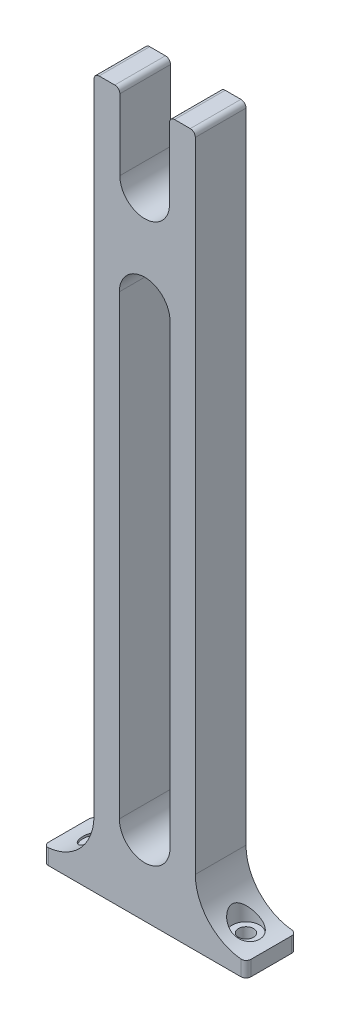
SolidWorks part; units mm, degrees
ref_plane "Front Plane" through (0, 0, 0) normal (0, 0, 1) x (1, 0, 0)
ref_plane "Top Plane" through (0, 0, 0) normal (0, 1, 0) x (1, 0, 0)
ref_plane "Right Plane" through (0, 0, 0) normal (1, 0, 0) x (0, 0, -1)
sketch "Sketch2" plane through (0, 0, 0) normal (0, 1, 0) x (1, 0, 0)
  line L1 (10, -5) -> (-10, -5)
  line L2 (10, -5) -> (10, 5)
  line L3 (10, 5) -> (-10, 5)
  line L4 (-10, -5) -> (-10, 5)
  line L5 (10, -5) -> (-10, 5) construction
  line L6 (10, 5) -> (-10, -5) construction
  point P0 (0, 0)
  dimension "D1" = 10
  dimension "D2" = 20
extrude "Boss-Extrude1" add sketch "Sketch2" along normal blind 140
sketch "Sketch3" plane through (0, 0, 5) normal (0, 0, 1) x (1, 0, 0)
  line L0 (-4.9, 140) -> (-4.9, 125)
  line L1 (-10, 140) -> (10, 140) construction
  line L2 (4.9, 125) -> (4.9, 140)
  line L3 (4.9, 140) -> (-4.9, 140)
  line L4 (-10, 0) -> (10, 0) construction
  arc A0 (-4.9, 125) -> (4.9, 125) centre (0, 125) ccw
  dimension "D2" = 4.9
  dimension "D1" = 125
extrude "Cut-Extrude1" cut sketch "Sketch3" against normal up to surface (10 mm away) up to face at (0, 70, -5)
sketch "Sketch5" plane through (0, 0, 5) normal (0, 0, 1) x (1, 0, 0)
  line L0 (0, 0) -> (0, 120.1) construction
  line L1 (-5, 15) -> (5, 15)
  line L2 (-5, 15) -> (-5, 105.1)
  line L3 (-5, 105.1) -> (5, 105.1)
  line L4 (5, 15) -> (5, 105.1)
  line L5 (-5, 15) -> (5, 105.1) construction
  line L6 (-5, 105.1) -> (5, 15) construction
  arc A0 (-5, 105.1) -> (5, 105.1) centre (0, 105.1) cw
  arc A1 (-5, 15) -> (5, 15) centre (0, 15) ccw
  arc A2 (-4.9, 125) -> (4.9, 125) centre (0, 125) ccw construction
  point P0 (0, 60.05)
  point P7 (0, 110.1)
  point P14 (0, 60.05)
  dimension "D1" = 5
  dimension "D2" = 10
extrude "Cut-Extrude2" cut sketch "Sketch5" against normal up to surface (10 mm away) contours L1 A1 | L1 L4 L3 L2 | A0 L3 region at (0, 60.05, 5) region at (0, 12.8779, 5) region at (0, 107.2221, 5) up to face at (0, 100.6375, -5)
sketch "Sketch6" plane through (10, 0, 0) normal (1, 0, 0) x (0, 0, -1)
  line L0 (5, 140) -> (5, 0) construction
  line L1 (-5, 0) -> (5, 0)
  line L2 (-5, 0) -> (-5, 3)
  line L3 (-5, 3) -> (5, 3)
  line L4 (5, 0) -> (5, 3)
  dimension "D1" = 3
extrude "Boss-Extrude2" add sketch "Sketch6" along normal blind 10
ref_plane "Plane1" through (0, 3, 0) normal (0, 1, 0) x (1, 0, 0)
fillet "Fillet2" radius 10 1 edges at (10, 3, 0)
sketch "Sketch19" plane through (0, 3, 0) normal (0, 1, 0) x (1, 0, 0)
  line L0 (15, 5) -> (15, -5) construction
  line L1 (10, -5) -> (20, -5) construction
  line L2 (20, 5) -> (10, 5) construction
  circle A0 centre (15, 0) radius 1.5
  circle A1 centre (15, 0) radius 2.7
  dimension "D1" = 3
  dimension "D2" = 5.4
extrude "Cut-Extrude5" cut sketch "Sketch19" against normal through all both and the other way through all contours A0
extrude "Cut-Extrude7" cut sketch "Sketch19<5>" along normal through all
sketch "Sketch19<5>" plane through (0, 3, 0) normal (0, 1, 0) x (1, 0, 0) same geometry as "Sketch19"
mirror "Mirror16" about plane through (0, 0, 0) normal (1, 0, 0) of "Boss-Extrude2"
fillet "Fillet1" radius 1 4 edges at (20, 1.5, -5) (20, 1.5, 5) (-20, 1.5, -5) (-20, 1.5, 5)
fillet "Fillet3" radius 10 1 edges at (-10, 3, 0)
sketch "Sketch20" plane through (0, 3, 0) normal (0, 1, 0) x (1, 0, 0)
  line L0 (-14.5, 5) -> (-14.5, -5) construction
  line L1 (-10, 5) -> (-19, 5) construction
  line L2 (-19, -5) -> (-10, -5) construction
  circle A0 centre (-14.5, 0) radius 1.5
  circle A1 centre (-14.5, 0) radius 2.7
  dimension "D1" = 3
  dimension "D2" = 5.4
extrude "Cut-Extrude8" cut sketch "Sketch20" against normal through all both and the other way through all contours A0
extrude "Cut-Extrude9" cut sketch "Sketch20<3>" along normal through all
sketch "Sketch20<3>" plane through (0, 3, 0) normal (0, 1, 0) x (1, 0, 0) same geometry as "Sketch20"
fillet "Fillet4" radius 1 4 edges at (-4.9, 140, 0) (4.9, 140, 0) (10, 140, 0) (-10, 140, 0)
